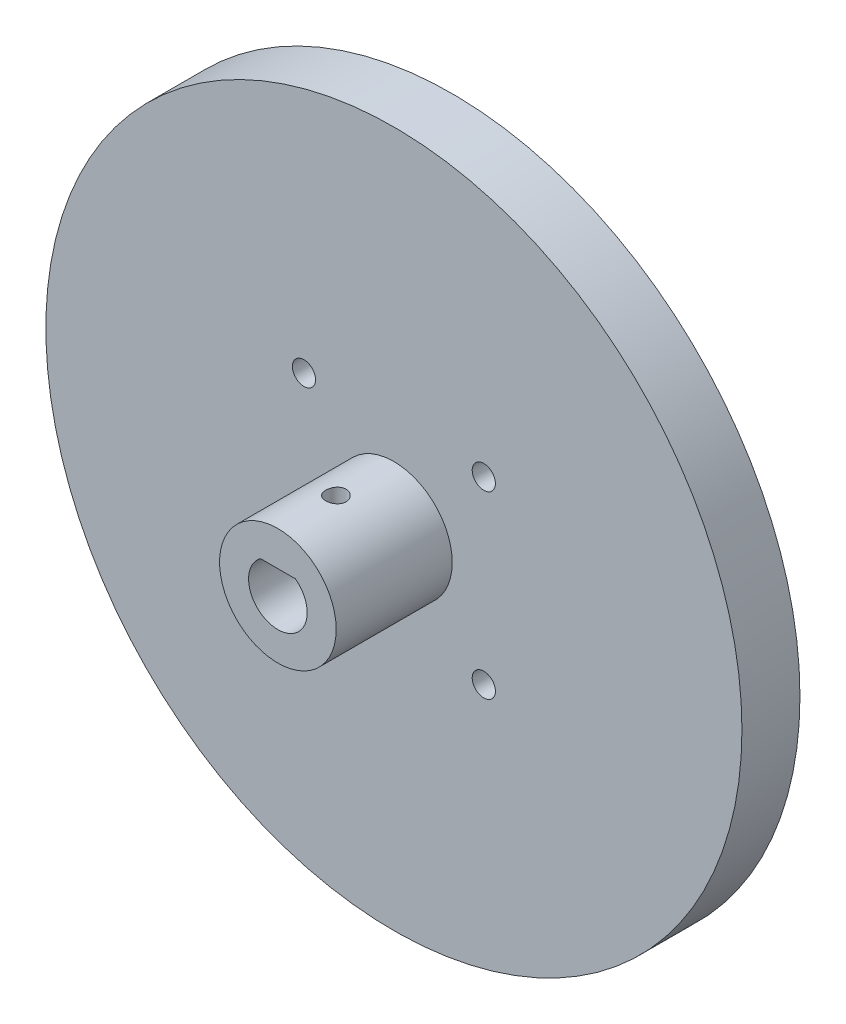
SolidWorks part; units mm, degrees
ref_plane "Front Plane" through (0, 0, 0) normal (0, 0, 1) x (1, 0, 0)
ref_plane "Top Plane" through (0, 0, 0) normal (0, 1, 0) x (1, 0, 0)
ref_plane "Right Plane" through (0, 0, 0) normal (1, 0, 0) x (0, 0, -1)
sketch "Sketch1" plane through (0, 0, 0) normal (0, 0, 1) x (1, 0, 0)
  line L1 (15.5, -15.5) -> (-15.5, -15.5) construction
  line L2 (15.5, -15.5) -> (15.5, 15.5) construction
  line L3 (15.5, 15.5) -> (-15.5, 15.5) construction
  line L4 (-15.5, -15.5) -> (-15.5, 15.5) construction
  line L5 (15.5, -15.5) -> (-15.5, 15.5) construction
  line L6 (15.5, 15.5) -> (-15.5, -15.5) construction
  circle A0 centre (0, 0) radius 60
  circle A1 centre (-15.5, 15.5) radius 2
  circle A2 centre (15.5, 15.5) radius 2
  circle A3 centre (15.5, -15.5) radius 2
  circle A4 centre (-15.5, -15.5) radius 2
  dimension "D1" = 120
  dimension "D3" = 4
  dimension "D4" = 2
  dimension "D2" = 31
  dimension "D5" = 2
extrude "Boss-Extrude1" add sketch "Sketch1" along normal blind 10
sketch "Sketch2" plane through (0, 0, 10) normal (0, 0, 1) x (1, 0, 0)
  line L0 (-3.0166, 4.05) -> (3.0166, 4.05)
  line L1 (0, 4.05) -> (0, -5.05)
  circle A0 centre (0, 0) radius 5.05
  circle A1 centre (0, 0) radius 10.05
  dimension "D1" = 10.1
  dimension "D2" = 9.1
  dimension "D3" = 5
extrude "Boss-Extrude2" add sketch "Sketch2" along normal blind 20 contours A1 A0 | L0 A0 region at (0, 4.4536, 10) region at (-9.7657, 0, 10)
sketch "Sketch3" plane through (0, 4.05, 0) normal (0, -1, 0) x (-1, 0, 0)
  line L0 (-10.05, -30) -> (10.05, -30) construction
  circle A0 centre (0, -20) radius 1.75
  point P4 (0, 0)
  point P6 (0, 0)
  dimension "D2" = 3.5
  dimension "D1" = 10
extrude "Cut-Extrude1" cut sketch "Sketch3" against normal blind 20 and the other way blind 20
